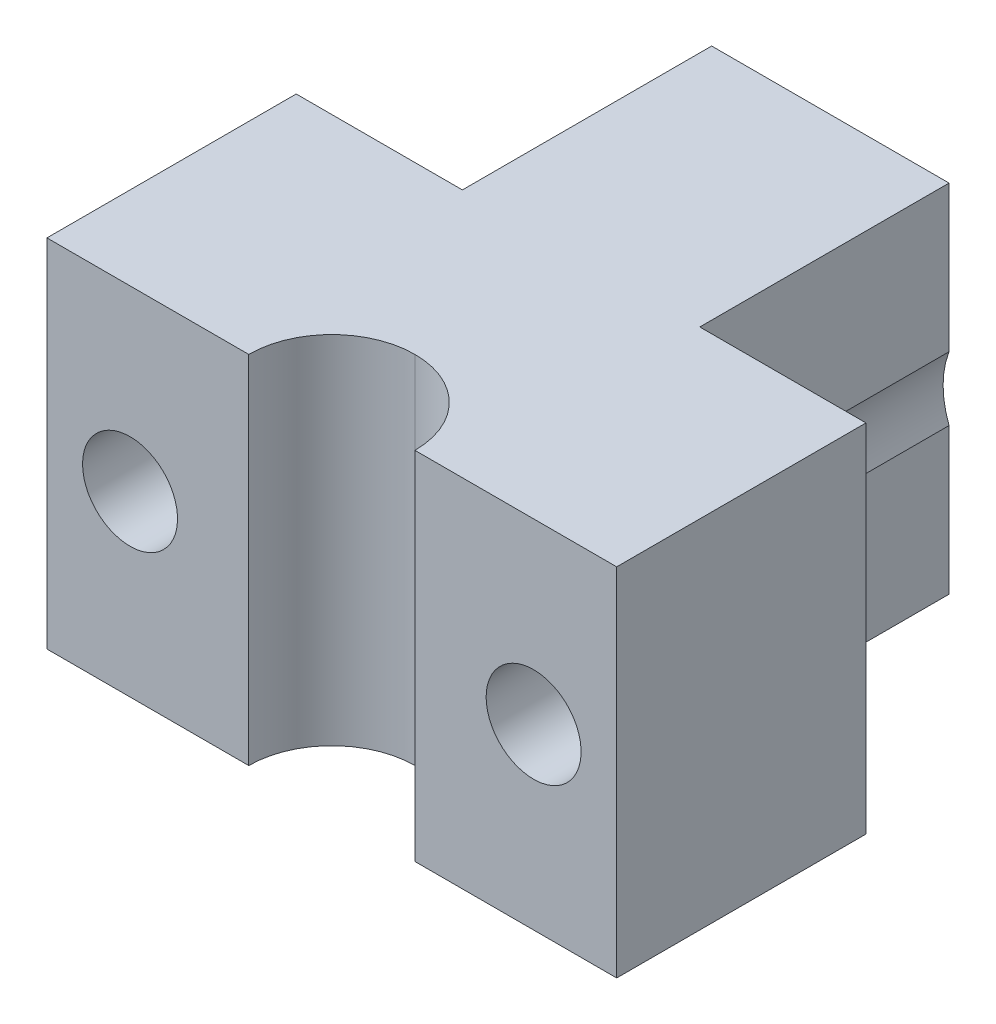
SolidWorks part; units mm, degrees
ref_plane "Спереди" through (0, 0, 0) normal (0, 0, 1) x (1, 0, 0)
ref_plane "Сверху" through (0, 0, 0) normal (0, 1, 0) x (1, 0, 0)
ref_plane "Справа" through (0, 0, 0) normal (1, 0, 0) x (0, 0, -1)
sketch "Эскиз1" plane through (0, 0, 0) normal (0, 1, 0) x (1, 0, 0)
  line L1 (-24, -10) -> (24, -10)
  line L2 (-24, -10) -> (-24, 10)
  line L3 (-24, 10) -> (24, 10)
  line L4 (24, -10) -> (24, 10)
  line L5 (-24, -10) -> (24, 10) construction
  line L6 (-24, 10) -> (24, -10) construction
  point P0 (0, 0)
  dimension "D1" = 48
  dimension "D2" = 20
extrude "Бобышка-Вытянуть1" add sketch "Эскиз1" along normal blind 30
sketch "Эскиз2" plane through (0, 0, 10) normal (0, 0, 1) x (1, 0, 0)
  line L0 (-7, 30) -> (-7, 0)
  line L1 (-24, 30) -> (24, 30) construction
  line L2 (-24, 0) -> (24, 0) construction
  line L3 (-7, 0) -> (7, 0)
  line L4 (7, 0) -> (7, 30)
  line L5 (7, 30) -> (-7, 30)
  dimension "D1" = 17
  dimension "D2" = 14
extrude "Вырез-Вытянуть1" cut sketch "Эскиз2" against normal blind 7
sketch "Эскиз7" plane through (24, 0, 0) normal (1, 0, 0) x (0, 0, -1)
  line L1 (32, 30) -> (32, 0)
  line L2 (32, 0) -> (10, 0)
  line L3 (-10, 0) -> (10, 0)
  line L4 (10, 0) -> (10.066, 0.2736)
  line L5 (10, 30) -> (32, 30)
  line L8 (10, 0) -> (10, 30)
  dimension "D3" = 22
extrude "Бобышка-Вытянуть2" add sketch "Эскиз7" against normal blind 48
sketch "Эскиз8" plane through (24, 0, 0) normal (1, 0, 0) x (0, 0, -1)
  line L0 (11, 0) -> (11, 30)
  line L1 (-10, 30) -> (32, 30) construction
  line L2 (11, 30) -> (32, 30)
  line L3 (11, 0) -> (32, 0)
  line L4 (32, 0) -> (32, 30)
  line L5 (-10, 0) -> (32, 0) construction
  point P16 (11, 0)
extrude "Вырез-Вытянуть2" cut sketch "Эскиз8" against normal blind 14
sketch "Эскиз9" plane through (-24, 0, 0) normal (-1, 0, 0) x (0, 0, 1)
  line L0 (-11, 0) -> (-11, 30)
  line L1 (-32, 30) -> (10, 30) construction
  line L2 (-11, 30) -> (-32, 30)
  line L3 (-32, 0) -> (10, 0) construction
  line L4 (-11, 0) -> (-32, 0)
  line L5 (-32, 0) -> (-32, 30)
  point P15 (-11, 0)
extrude "Вырез-Вытянуть3" cut sketch "Эскиз9" against normal blind 14
sketch "Эскиз11" plane through (-10, 0, 0) normal (-1, 0, 0) x (0, 0, 1)
  line L0 (-32, 30) -> (-11, 0) construction
  line L2 (-32, 0) -> (-11, 0) construction
  line L3 (-16.4, 4.9) -> (-16.4, 25.1)
  line L6 (-16.4, 4.9) -> (-26.6, 4.9)
  line L7 (-16.4, 25.1) -> (-26.6, 25.1)
  line L8 (-26.6, 4.9) -> (-26.6, 25.1)
  line L9 (-16.4, 4.9) -> (-26.6, 25.1) construction
  line L10 (-16.4, 25.1) -> (-26.6, 4.9) construction
  point P7 (-21.5, 15)
  point P8 (-21.5, 15)
  dimension "D1" = 20.2
  dimension "D2" = 10.2
extrude "Вырез-Вытянуть4" cut sketch "Эскиз11" against normal through all
sketch "Эскиз13" plane through (0, 0, -11) normal (0, 0, -1) x (-1, 0, 0)
  line L0 (24, 15) -> (10, 15) construction
  line L1 (24, 0) -> (24, 30) construction
  line L2 (10, 0) -> (10, 30) construction
  circle A0 centre (17, 15) radius 4
extrude "Вырез-Вытянуть5" cut sketch "Эскиз13" against normal through all
sketch "Эскиз14" plane through (0, 0, -11) normal (0, 0, -1) x (-1, 0, 0)
  line L0 (-24, 15) -> (-10, 15) construction
  line L1 (-24, 30) -> (-24, 0) construction
  line L2 (-10, 30) -> (-10, 0) construction
  circle A0 centre (-17, 15) radius 4
extrude "Вырез-Вытянуть6" cut sketch "Эскиз14" against normal through all
fillet "Скругление1" radius 7 2 edges at (-7, 15, 3) (7, 15, 3)
sketch "Sketch1" plane through (10, 0, 0) normal (1, 0, 0) x (0, 0, -1)
  line L0 (16.4, 25.1) -> (26.6, 4.9) construction
  line L2 (26.6, 4.9) -> (16.4, 4.9)
  line L3 (26.6, 4.9) -> (26.6, 25.1)
  line L4 (26.6, 25.1) -> (16.4, 25.1)
  line L5 (16.4, 4.9) -> (16.4, 25.1)
  line L6 (26.6, 4.9) -> (16.4, 25.1) construction
  line L7 (26.6, 25.1) -> (16.4, 4.9) construction
  point P4 (21.5, 15)
extrude "Boss-Extrude1" add sketch "Sketch1" against normal blind 4
sketch "Эскиз20" plane through (0, 0, -11) normal (0, 0, -1) x (-1, 0, 0)
  circle A0 centre (-17, 15) radius 7.5
  circle A1 centre (17, 15) radius 7.5
  dimension "D1" = 15
extrude "Вырез-Вытянуть8" cut sketch "Эскиз20" along normal through all
